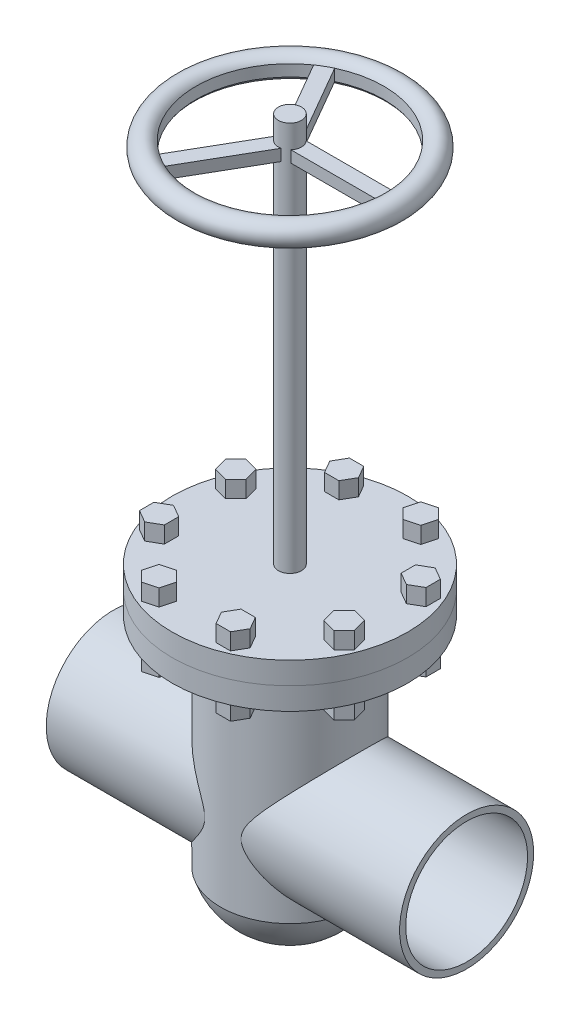
SolidWorks part; units mm, degrees
ref_plane "Front Plane" through (0, 0, 0) normal (0, 0, 1) x (1, 0, 0)
ref_plane "Top Plane" through (0, 0, 0) normal (0, 1, 0) x (1, 0, 0)
ref_plane "Right Plane" through (0, 0, 0) normal (1, 0, 0) x (0, 0, -1)
sketch "Weld End Sketch" plane through (0, 0, 0) normal (1, 0, 0) x (0, 0, -1)
  circle A0 centre (0, 0) radius 72.263
  dimension "A" = 144.526
extrude "Weld End" add sketch "Weld End Sketch" against normal mid plane 381
sketch "Body Sketch" plane through (0, 0, 0) normal (0, 0, 1) x (1, 0, 0)
  line L0 (-74.8754, 162.814) -> (-74.8754, -72.263)
  line L1 (0, -199.4458) -> (0, 283.4066) construction
  line L2 (-190.5, -72.263) -> (190.5, -72.263) construction
  line L5 (0, -127.9652) -> (0, 162.814)
  line L6 (-74.8754, 162.814) -> (0, 162.814)
  arc A0 (-74.8754, -72.263) -> (0, -127.9652) centre (0, -49.79) ccw
  dimension "R*.3" = 55.7022
  dimension "(A+2* t)*0.95" = 149.7508
  dimension "O/2+1.5* C1" = 162.814
revolve "Body" add sketch "Body Sketch" angle 360 about L1
sketch "Flange Bottom Sketch" plane through (0, 162.814, 0) normal (0, 1, 0) x (-1, 0, 0)
  circle A0 centre (0, 0) radius 127
  dimension "O" = 254
extrude "Flange Bottom" add sketch "Flange Bottom Sketch" along normal blind 23.876
sketch "Flange Top Sketch" plane through (0, 186.69, 0) normal (0, 1, 0) x (-1, 0, 0)
  circle A1 centre (0, 0) radius 127
  circle A2 centre (0, 0) radius 127
  dimension "D1" = 0
extrude "Flange Top" add sketch "Flange Top Sketch" along normal blind 23.876
ref_plane "Driver Plane" through (0, 599.948, 0) normal (0, 1, 0) x (-1, 0, 0)
sketch "Driver Path" plane through (0, 599.948, 0) normal (0, 1, 0) x (-1, 0, 0)
  circle A0 centre (0, 0) radius 124.46
  dimension "D" = 248.92
sketch "Driver Profile" plane through (0, 0, 0) normal (0, 0, 1) x (1, 0, 0)
  line L0 (124.46, 599.948) -> (-124.46, 599.948) construction
  line L1 (-101.2354, 606.171) -> (0, 606.171)
  line L2 (124.46, 599.948) -> (-124.46, 599.948) construction
  line L3 (-101.2354, 593.725) -> (0, 593.725)
  line L4 (0, 606.171) -> (0, 593.725)
  arc A0 (-101.2354, 606.171) -> (-101.2354, 593.725) centre (-112.014, 599.948) ccw
  dimension "D1" = 12.446
  dimension "D/20" = 12.446
sweep "Driver Sweep" add profiles "Driver Profile" path "Driver Path"
sketch "Centre Support Sketch" plane through (0, 606.171, 0) normal (0, 1, 0) x (-1, 0, 0)
  circle A0 centre (0, 0) radius 12.446
  dimension "D/10" = 24.892
extrude "Centre Support" add sketch "Centre Support Sketch" against normal up to surface (395.605 mm away) and the other way blind 24.892 up to face at (0, 210.566, 127)
sketch "Driver Cut Sketch" plane through (0, 606.171, 0) normal (0, 1, 0) x (-1, 0, 0)
  line L0 (0, 0) -> (0, 113.8697) construction
  line L1 (0, 0) -> (-104.7757, 0) construction
  line L2 (43.2617, 91.5262) -> (-2.5474, 12.1825)
  line L3 (-100.8948, -8.2973) -> (-9.2767, -8.2973)
  line L4 (57.6331, 83.2288) -> (11.8241, 3.8852)
  line L5 (-100.8948, 8.2973) -> (-9.2767, 8.2973)
  line L6 (57.6331, -83.2288) -> (11.8241, -3.8852)
  line L7 (43.2617, -91.5262) -> (-2.5474, -12.1825)
  circle A0 centre (0, 0) radius 101.2354 construction
  arc A1 (43.2617, 91.5262) -> (-100.8948, 8.2973) centre (0, 0) ccw
  circle A2 centre (0, 0) radius 12.446 construction
  arc A3 (-9.2767, -8.2973) -> (-2.5474, -12.1825) centre (0, 0) ccw
  arc A4 (-2.5474, 12.1825) -> (-9.2767, 8.2973) centre (0, 0) ccw
  arc A5 (11.8241, -3.8852) -> (11.8241, 3.8852) centre (0, 0) ccw
  arc A6 (57.6331, -83.2288) -> (57.6331, 83.2288) centre (0, 0) ccw
  arc A7 (-100.8948, -8.2973) -> (43.2617, -91.5262) centre (0, 0) ccw
  dimension "D/30" = 8.2973
extrude "Driver Cut" cut sketch "Driver Cut Sketch" against normal up to surface (12.446 mm away) up to face at (0, 593.725, 12.446)
ref_plane "Bolt Plane" through (0, 228.473, 0) normal (0, 1, 0) x (-1, 0, 0)
sketch "ID Cut Sketch" plane through (190.5, 0, 0) normal (1, 0, 0) x (0, 0, -1)
  circle A0 centre (0, 0) radius 65.7098
  dimension "A-2* t" = 131.4196
extrude "ID Cut" cut sketch "ID Cut Sketch" against normal through all
sketch "Bolt Sketch" plane through (0, 228.473, 0) normal (0, 1, 0) x (-1, 0, 0)
  line L0 (0, 0) -> (-127.3205, -52.7379) construction
  line L1 (0, 0) -> (-142.2485, 0) construction
  line L2 (-99.7328, -25.8248) -> (-113.144, -33.5677)
  line L3 (-113.144, -33.5677) -> (-113.144, -49.0536)
  line L4 (-113.144, -49.0536) -> (-99.7328, -56.7966)
  line L5 (-99.7328, -56.7966) -> (-86.3216, -49.0536)
  line L6 (-86.3216, -49.0536) -> (-86.3216, -33.5677)
  line L7 (-86.3216, -33.5677) -> (-99.7328, -25.8248)
  circle A0 centre (0, 0) radius 107.95 construction
  circle A2 centre (-99.7328, -41.3107) radius 13.4112 construction
  dimension "BC" = 215.9
  dimension "DH*1.2" = 26.8224
  dimension "Angle" = 22.5
extrude "Bolt" add sketch "Bolt Sketch" against normal blind 83.566
pattern_circular "Bolt Pattern" count 8 every 45 about axis through (0, 186.69, 0) along (0, -1, 0) of "Bolt"
sketch "Sketch1" plane through (0, 0, 0) normal (0, 0, 1) x (1, 0, 0)
  line L1 (127, 186.69) -> (-127, 186.69)
  line L2 (127, 186.69) -> (-127, 186.69)
  dimension "D1" = 0
split line "Split Line1"
sketch "CPointSketch" plane through (0, 0, 0) normal (0, 0, 1) x (1, 0, 0)
  line L0 (-190.5, 72.263) -> (-190.5, -72.263) construction
  line L1 (-190.5, 0) -> (190.5, 0) construction
  line L2 (190.5, -72.263) -> (190.5, 72.263) construction
  point P0 (-190.5, 0)
  point P1 (190.5, 0)
  point P8 (0, 0)
other "CPoint1" parameters "Diameter"=127, "StubLength"=0
ref_axis "Axis1" through (-200.5, 0, 0) along (1, 0, 0)
other "CPoint2" parameters "Diameter"=127, "StubLength"=0
ref_axis "Axis2" through (200.5, 0, 0) along (-1, 0, 0)
other "RPoint1"
sketch "Sketch2" plane through (0, 0, 0) normal (0, 1, 0) x (1, 0, 0)
  line L1 (195.1341, 138.8668) -> (-195.1341, 138.8668)
  line L2 (195.1341, 138.8668) -> (195.1341, -138.8668)
  line L3 (195.1341, -138.8668) -> (-195.1341, -138.8668)
  line L4 (-195.1341, 138.8668) -> (-195.1341, -138.8668)
  line L5 (195.1341, 138.8668) -> (-195.1341, -138.8668) construction
  line L6 (195.1341, -138.8668) -> (-195.1341, 138.8668) construction
  point P0 (0, 0)
equation "\"D1@Driver Profile\" = \"D/20@Driver Profile\""
equation "\"D2@Centre Support\" = \"D/10@Centre Support Sketch\""
